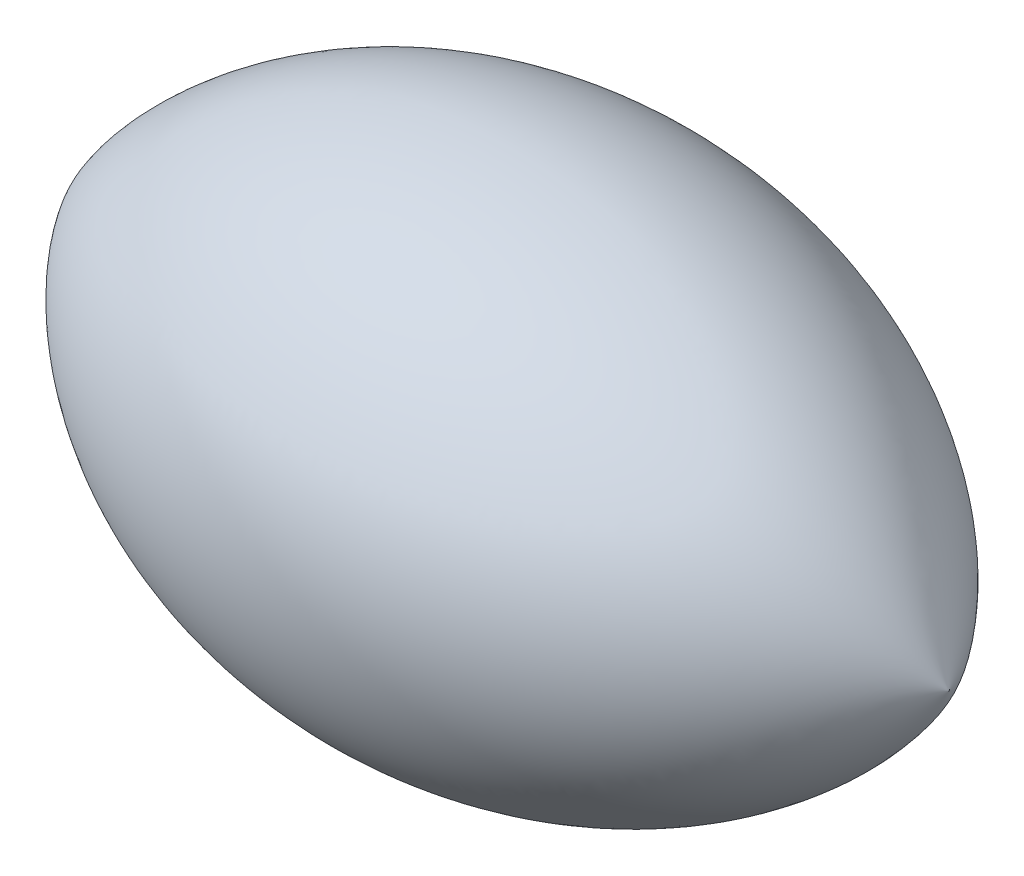
SolidWorks part; units mm, degrees
ref_plane "Front" through (0, 0, 0) normal (0, 0, 1) x (1, 0, 0)
ref_plane "Top" through (0, 0, 0) normal (0, 1, 0) x (1, 0, 0)
ref_plane "Right" through (0, 0, 0) normal (1, 0, 0) x (0, 0, -1)
sketch "Sketch1" plane through (0, 0, 0) normal (0, 0, 1) x (1, 0, 0)
  line L0 (-349.3403, 146.6027) -> (368.0527, 146.6027) construction
  line L1 (-349.3403, 146.6027) -> (368.0527, 146.6027)
  spline S0 degree 3 poles (-349.3403, 146.6027) (-206.6943, 425.1814) (224.0232, 421.1382) (368.0527, 146.6027) knots 0 0 0 0 1 1 1 1
revolve "Revolve1" add sketch "Sketch1" angle 360 about L0
